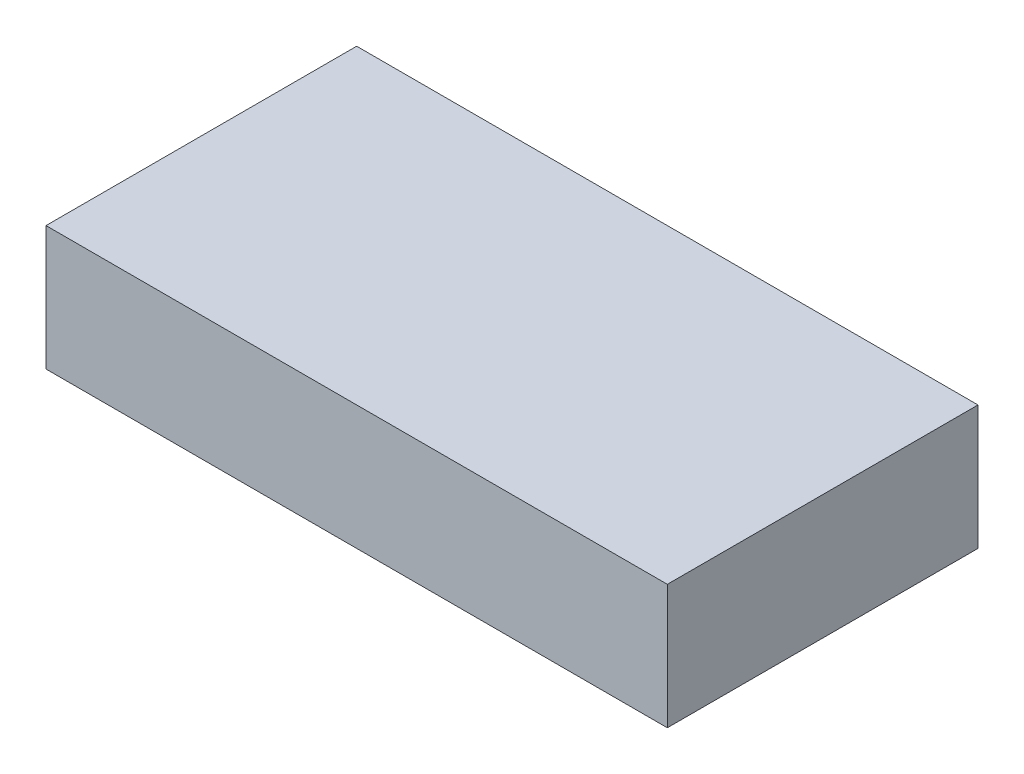
SolidWorks part; units mm, degrees
ref_plane "Front Plane" through (0, 0, 0) normal (0, 0, 1) x (1, 0, 0)
ref_plane "Top Plane" through (0, 0, 0) normal (0, 1, 0) x (1, 0, 0)
ref_plane "Right Plane" through (0, 0, 0) normal (1, 0, 0) x (0, 0, -1)
sketch "Sketch1" plane through (0, 0, 0) normal (0, 1, 0) x (1, 0, 0)
  line L1 (-5, 2.5) -> (5, 2.5)
  line L2 (-5, 2.5) -> (-5, -2.5)
  line L3 (-5, -2.5) -> (5, -2.5)
  line L4 (5, 2.5) -> (5, -2.5)
  line L5 (-5, 2.5) -> (5, -2.5) construction
  line L6 (-5, -2.5) -> (5, 2.5) construction
  line L7 (-4, -1.5) -> (4, -1.5)
  line L8 (-4, -1.5) -> (-4, 1.5)
  line L9 (-4, 1.5) -> (4, 1.5)
  line L10 (4, -1.5) -> (4, 1.5)
  line L11 (-4, -1.5) -> (4, 1.5) construction
  line L12 (-4, 1.5) -> (4, -1.5) construction
  circle A0 centre (-2.5, 0) radius 1.5
  circle A1 centre (2.5, 0) radius 1.5
  circle A2 centre (-2.5, 0) radius 0.75
  circle A3 centre (2.5, 0) radius 0.75
  circle A4 centre (0, 0) radius 1
  point P0 (0, 0)
  point P6 (0, 0)
  dimension "D5" = 1.5
  dimension "D1" = 5
  dimension "D2" = 10
  dimension "D3" = 1
  dimension "D4" = 1
  dimension "D6" = 2
extrude "Boss-Extrude1" add sketch "Sketch1" along normal blind 1 contours L2 L3 L4 L1
extrude "Boss-Extrude2" add sketch "Sketch1<3>" against normal blind 1 contours L4 L1 L2 L3 L10 L7 L8 L9 region at (0, 0, -2.3882)
sketch "Sketch1<3>" plane through (0, 0, 0) normal (0, 1, 0) x (1, 0, 0) same geometry as "Sketch1"
